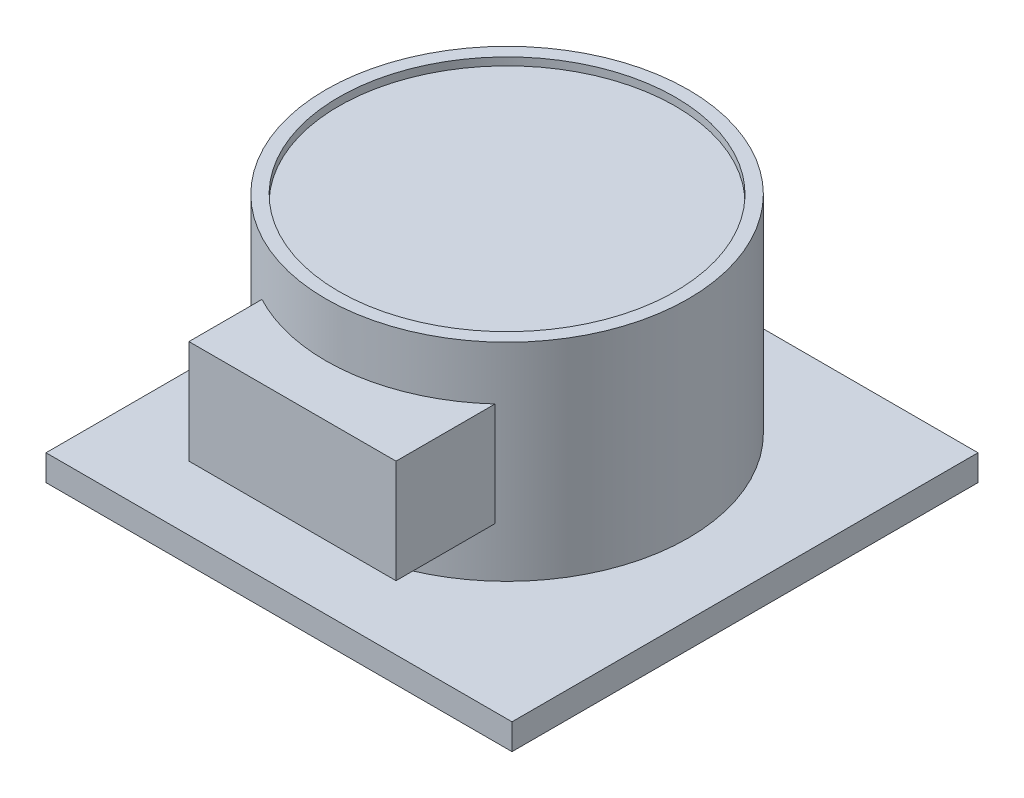
SolidWorks part; units mm, degrees
ref_plane "Front Plane" through (0, 0, 0) normal (0, 0, 1) x (1, 0, 0)
ref_plane "Top Plane" through (0, 0, 0) normal (0, 1, 0) x (1, 0, 0)
ref_plane "Right Plane" through (0, 0, 0) normal (1, 0, 0) x (0, 0, -1)
sketch "Sketch1" plane through (0, 0, 0) normal (0, 1, 0) x (1, 0, 0)
  line L1 (-139.5918, 84.4898) -> (40.4082, 84.4898)
  line L2 (-139.5918, 84.4898) -> (-139.5918, -95.5102)
  line L3 (-139.5918, -95.5102) -> (40.4082, -95.5102)
  line L4 (40.4082, 84.4898) -> (40.4082, -95.5102)
  dimension "D1" = 180
extrude "Boss-Extrude1" add sketch "Sketch1" along normal blind 10
sketch "Sketch2" plane through (0, 10, 0) normal (0, 1, 0) x (1, 0, 0)
  circle A0 centre (-57.0067, 0) radius 70
  dimension "D1" = 140
extrude "Boss-Extrude2" add sketch "Sketch2" along normal blind 80
sketch "Sketch3" plane through (0, 0, 0) normal (0, 0, 1) x (1, 0, 0)
  line L1 (-89.8939, 69.2885) -> (-9.8939, 69.2885)
  line L2 (-89.8939, 69.2885) -> (-89.8939, 29.2885)
  line L3 (-89.8939, 29.2885) -> (-9.8939, 29.2885)
  line L4 (-9.8939, 69.2885) -> (-9.8939, 29.2885)
  dimension "D1" = 40
  dimension "D2" = 80
extrude "Boss-Extrude3" add sketch "Sketch3" along normal blind 90
sketch "Sketch4" plane through (0, 90, 0) normal (0, 1, 0) x (1, 0, 0)
  circle A2 centre (-57.0067, 0) radius 65
  circle A3 centre (-57.0067, 0) radius 65
  dimension "D1" = 5
extrude "Cut-Extrude1" cut sketch "Sketch4" against normal blind 3
